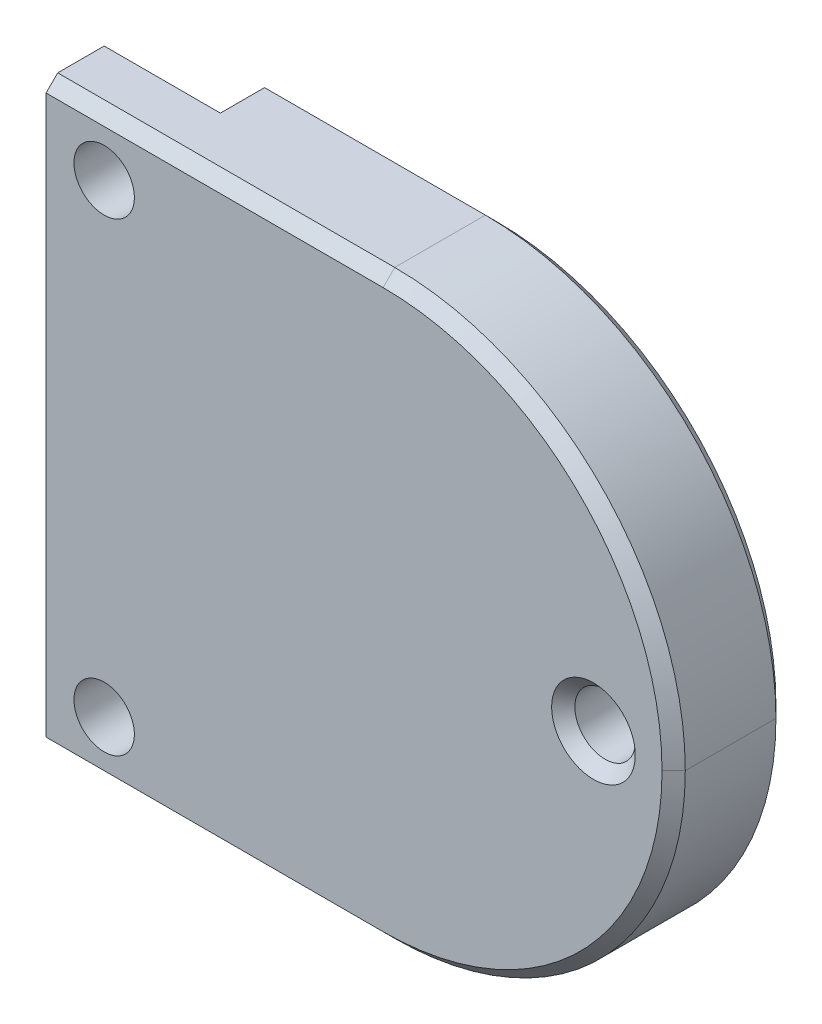
SolidWorks part; units mm, degrees
ref_plane "Front Plane" through (0, 0, 0) normal (0, 0, 1) x (1, 0, 0)
ref_plane "Top Plane" through (0, 0, 0) normal (0, 1, 0) x (1, 0, 0)
ref_plane "Right Plane" through (0, 0, 0) normal (1, 0, 0) x (0, 0, -1)
sketch "Sketch1" plane through (0, 0, 0) normal (0, 0, 1) x (1, 0, 0)
  line L1 (0, 0) -> (54, 0)
  line L2 (0, 0) -> (0, 50)
  line L3 (0, 50) -> (54, 50)
  line L4 (54, 0) -> (54, 50)
  circle A0 centre (5, 45) radius 2.6
  circle A1 centre (5, 5) radius 2.6
  dimension "D3" = 5.2
  dimension "D4" = 5
  dimension "D5" = 5
  dimension "D1" = 54
  dimension "D2" = 50
  dimension "D6" = 2
extrude "Boss-Extrude1" add sketch "Sketch1" along normal blind 5
ref_plane "Plane1" through (10, 0, 0) normal (-1, 0, 0) x (0, 0, 1)
sketch "Sketch2" plane through (10, 0, 0) normal (-1, 0, 0) x (0, 0, 1)
  line L0 (0, 50) -> (0, 0) construction
  line L1 (0, 50) -> (-4.8, 50)
  line L2 (0, 50) -> (0, 0)
  line L3 (0, 0) -> (-4.8, 0)
  line L4 (-4.8, 50) -> (-4.8, 0)
  line L5 (5, 50) -> (0, 50) construction
  line L6 (5, 0) -> (0, 0) construction
  dimension "D1" = 4.8
extrude "Boss-Extrude2" add sketch "Sketch2" against normal blind 44
sketch "Sketch3" plane through (0, 0, -4.8) normal (0, 0, -1) x (-1, 0, 0)
  line L0 (0, 25) -> (-54, 25) construction
  line L1 (0, 50) -> (0, 0) construction
  line L2 (-54, 50) -> (-54, 0) construction
  circle A0 centre (-47.1, 25) radius 2.6
  dimension "D1" = 5.2
  dimension "D2" = 47.1
extrude "Cut-Extrude1" cut sketch "Sketch3" against normal blind 10
fillet "Fillet1" radius 25 2 edges at (54, 0, 0.1) (54, 50, 0.1)
chamfer "Chamfer1" distance 1 angle 45 1 edges at (44.5, 25, 5)
chamfer "Chamfer2" distance 1 angle 45 4 edges at (14.5, 0, 5) (46.6777, 7.3223, 5) (14.5, 50, 5) (46.6777, 42.6777, 5)
chamfer "Chamfer3" distance 1 angle 45 4 edges at (19.5, 0, -4.8) (19.5, 50, -4.8) (46.6777, 7.3223, -4.8) (46.6777, 42.6777, -4.8)
